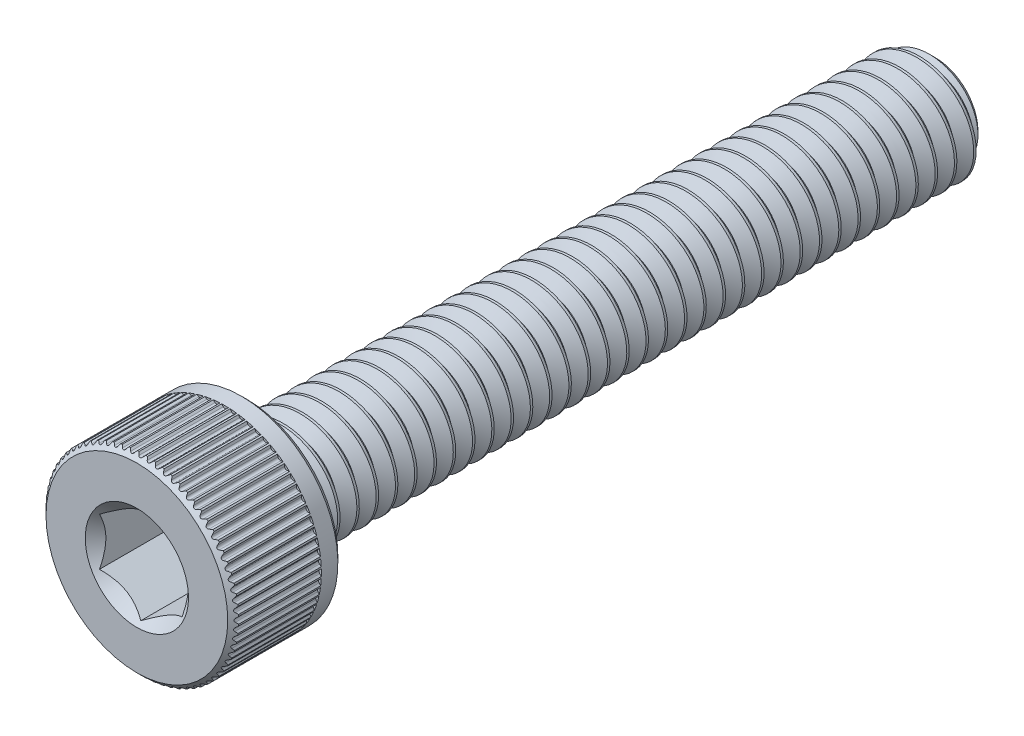
SolidWorks part; units mm, degrees
ref_plane "Front Plane" through (0, 0, 0) normal (0, 0, 1) x (1, 0, 0)
ref_plane "Top Plane" through (0, 0, 0) normal (0, 1, 0) x (1, 0, 0)
ref_plane "Right Plane" through (0, 0, 0) normal (1, 0, 0) x (0, 0, -1)
sketch "Sketch1" plane through (0, 0, 0) normal (1, 0, 0) x (0, 0, -1)
  line L0 (-14.5, 0) -> (14.5, 0) construction
  line L1 (14.5, 0) -> (14.5, 1.5453) construction
  line L2 (14.5, 1.5453) -> (14.0453, 2) construction
  line L3 (14.0453, 2) -> (13.975, 2) construction
  line L4 (13.975, 2) -> (-10.5, 2) construction
  line L5 (-10.5, 2) -> (-10.5, 3.5) construction
  line L6 (-10.5, 3.5) -> (-14.5, 3.5) construction
  line L7 (-14.5, 3.5) -> (-14.5, 0) construction
  line L8 (14.5, 1.5453) -> (14.5, 2) construction
  line L9 (14.4563, 2.0758) -> (14.8063, 1.4696) construction
  line L10 (14.8063, 1.4696) -> (15.1563, 2.0758) construction
  line L11 (15.1563, 2.0758) -> (14.4563, 2.0758) construction
  line L12 (14.8063, 2.0758) -> (14.8063, 2) construction
  line L13 (14.8063, 1.4696) -> (14.8063, 1.5453) construction
  line L14 (14.7625, 1.5453) -> (14.85, 1.5453) construction
  line L15 (14.5, 2) -> (15.1125, 2) construction
  line L16 (14.4781, 2.0379) -> (15.1344, 2.0379) construction
  line L17 (14.5, 0) -> (14.5, -2) construction
  line L18 (-10.7, 3.5) -> (-10.5, 3.3) construction
  line L19 (-14.3, 3.5) -> (-14.5, 3.3) construction
  line L20 (-10.5, 2) -> (-10.5, 0) construction
  line L21 (-10.5, 1) -> (-2.1667, 1) construction
  line L22 (-2.1667, 1) -> (6.1667, 1) construction
  line L23 (6.1667, 1) -> (14.5, 1) construction
  line L24 (-2.1667, 1) -> (-2.1667, 2) construction
  line L25 (-2.1667, 2) -> (-2.1667, 3.5) construction
  line L26 (6.1667, 1) -> (6.1667, 3.5) construction
  point P0 (-14.5, 1.5)
  point P3 (12.75, 2)
  point P4 (0, 0)
  point P18 (6.1667, 2)
  point P22 (14.8063, 1.5453)
  point P24 (13.975, 2)
  point P25 (14.8063, 2)
  point P28 (14.8063, 2.0379)
  point P29 (12.75, -2)
  point P30 (-2.1667, 2)
  point P31 (-12.5, 3.5)
  point P37 (-11.2, 3.5)
  point P38 (-14.2, 3.5)
  point P45 (-2.1667, 1)
  point P46 (6.1667, 1)
  dimension "D2" = 0.0875
  dimension "D7" = 0.2
  dimension "D8" = 0.2
  dimension "D9" = 0.2
  dimension "D10" = 0.1
  dimension "D11" = 0.5
  dimension "Drive Size" = 3
  dimension "Head Diameter" = 7
  dimension "Head Height" = 4
  dimension "Thread Pitch" = 0.7
  dimension "Thread Size" = 4
  dimension "Length" = 25
  dimension "D12" = 0.525
  dimension "D4" = 1.75
  dimension "D3" = 45
sketch "Sketch2" plane through (0, 0, 0) normal (1, 0, 0) x (0, 0, -1)
  line L0 (-14.5, 0) -> (-14.5, 3.3)
  line L1 (-14.3, 3.5) -> (-10.7, 3.5)
  line L2 (-10.5, 3.3) -> (-10.5, 2.2)
  line L4 (14.0453, 2) -> (14.5, 1.5453)
  line L5 (14.5, 1.5453) -> (14.5, 0)
  line L6 (-10.5, 3.5) -> (-14.5, 3.5) construction
  line L7 (14.5, 0) -> (-14.5, 0)
  line L8 (-14.3, 3.5) -> (-14.5, 3.3) construction
  line L10 (-14.3, 3.5) -> (-14.5, 3.3)
  line L14 (-10.7, 3.5) -> (-10.5, 3.3) construction
  line L16 (-10.7, 3.5) -> (-10.5, 3.3)
  line L17 (-10.5, 2) -> (-10.5, 3.5) construction
  line L19 (-10.3, 2) -> (14.0453, 2)
  line L20 (13.975, 2) -> (-10.5, 2) construction
  arc A1 (-10.5, 2.2) -> (-10.3, 2) centre (-10.3, 2.2) ccw
  dimension "D3" = 0.2
revolve "Revolve1" add sketch "Sketch2" angle 360 about L7
sketch "Sketch3" plane through (0, 0, 14.5) normal (0, 0, 1) x (1, 0, 0)
  line L1 (1.5, -0.866) -> (1.5, 0.866)
  line L2 (1.5, 0.866) -> (0, 1.7321)
  line L3 (0, 1.7321) -> (-1.5, 0.866)
  line L4 (-1.5, 0.866) -> (-1.5, -0.866)
  line L5 (-1.5, -0.866) -> (0, -1.7321)
  line L6 (0, -1.7321) -> (1.5, -0.866)
  circle A0 centre (0, 0) radius 1.5 construction
  circle A1 centre (0, 0) radius 3.5 construction
  circle A2 centre (0, 0) radius 3.5 construction
  circle A3 centre (0, 0) radius 1.7321 construction
  point P13 (0, 0)
extrude "Cut-Extrude1" cut sketch "Sketch3" against normal offset from surface (3 mm away) 1 up to face at (0, 3.3, 10.5)
sketch "Sketch4" plane through (0, 0, 14.5) normal (0, 0, 1) x (1, 0, 0)
  circle A0 centre (0, 0) radius 1.875
  dimension "D1" = 3.75
extrude "Cut-Extrude2" cut sketch "Sketch4" against normal up to vertex (2 mm away) draft 45 up to point (0, 3.5, 12.5)
sketch "Sketch11" plane through (0, 0, 0) normal (1, 0, 0) x (0, 0, -1)
  line L0 (-14.5, 0) -> (14.5, 0) construction
  line L1 (-14.5, 0) -> (14.5, 0) construction
  line L2 (-5.8125, 0) -> (-5.8125, 2) construction
  line L3 (13.975, 2) -> (-10.5, 2) construction
  line L4 (9.8125, 0) -> (9.8125, 2) construction
  line L6 (14.5, 1.5453) -> (14.5, 2) construction
  point P2 (-5.8125, 0)
  point P3 (9.8125, 0)
  dimension "D1" = 4.6875
  dimension "D2" = 4.6875
sketch "Sketch6" plane through (0, 0, -14.5) normal (0, 0, -1) x (-1, 0, 0)
  circle A0 centre (0, 0) radius 2
curve "Helix/Spiral1" pitch 0.7 height 25.7 turns 36.7143
sketch "Sketch10" plane through (0, 0, 0) normal (1, 0, 0) x (0, 0, -1)
  line L0 (-10.3, -3.5) -> (-10.3, 3.5)
  line L5 (-14.5, 0) -> (14.5, 0) construction
  line L6 (-10.3, 2) -> (-10.3, -2) construction
  point P3 (-10.3, 0)
split "Split1" trim tools "Sketch10" bodies to split 106 resulting bodies 114 115
sketch "Sketch7" plane through (0, 0, 0) normal (1, 0, 0) x (0, 0, -1)
  line L0 (14.4781, 2.0379) -> (15.1344, 2.0379)
  line L1 (15.1344, 2.0379) -> (14.85, 1.5453)
  line L2 (14.85, 1.5453) -> (14.7625, 1.5453)
  line L3 (14.7625, 1.5453) -> (14.4781, 2.0379)
sweep "Cut-Sweep1" cut profiles "Sketch7" path "Helix/Spiral1"
sketch "Sketch8" plane through (0, 0, 0) normal (1, 0, 0) x (0, 0, -1)
  line L0 (-10.5, 0) -> (-10.5, 2)
  line L1 (-10.3, -2) -> (-10.3, 2) construction
  line L2 (-10.5, 2) -> (-10.3, 2)
  line L4 (-10.3, 2) -> (-9.1453, 0)
  line L5 (-9.1453, 0) -> (-10.5, 0)
  line L6 (13.975, 2) -> (-10.5, 2) construction
  line L7 (-14.5, 0) -> (14.5, 0) construction
  dimension "D1" = 60
revolve "Revolve2" add sketch "Sketch8" angle 360 about L5
ref_plane "Plane1" through (0, 0, 14.5) normal (0, 0, 1) x (1, 0, 0)
sketch "Sketch12" plane through (0, 0, 14.5) normal (0, 0, 1) x (1, 0, 0)
  line L0 (0, 0) -> (0.1221, 3.4979) construction
  line L1 (0, 0) -> (-0.1221, 3.4979) construction
  line L2 (0, 3.4125) -> (0, 3.5875) construction
  line L3 (-0.2118, 3.5875) -> (0.2118, 3.5875)
  line L4 (-0.2118, 3.5875) -> (-0.0628, 3.4385)
  line L5 (0.0628, 3.4385) -> (0.2118, 3.5875)
  circle A0 centre (0, 0) radius 3.5 construction
  arc A1 (-0.0628, 3.4385) -> (0.0628, 3.4385) centre (0, 3.5013) ccw
  point P9 (0, 3.5875)
  point P13 (0, 3.5)
  dimension "D1" = 4
  dimension "D2" = 0.0875
extrude "Cut-Extrude3" cut sketch "Sketch12" against normal blind 3.2
pattern_circular "CirPattern1" count 72 over 360 about axis through (0, 0, 0) along (0, 0, 1) of "Cut-Extrude3"
equation "\"D2@Sketch1\" = \"Thread Pitch@Sketch1\" / 8"
equation "\"D4@Helix/Spiral1\" = \"Thread Pitch@Sketch1\""
equation "\"D7@Sketch1\" = \"Head Height@Sketch1\" * .05"
equation "\"D8@Sketch1\"=\"D7@Sketch1\""
equation "\"D9@Sketch1\"=\"D7@Sketch1\""
equation "\"D10@Sketch1\"=\"D7@Sketch1\"/2"
equation "\"D11@Sketch1\"=\"D10@Sketch1\"*5"
equation "\"D4@Sketch1\"=\"Thread Pitch@Sketch1\"*2.5"
equation "\"D12@Sketch1\"=\"Thread Pitch@Sketch1\"*.75"
equation "\"D3@Helix/Spiral1\"=\"Length@Sketch1\"+\"Thread Pitch@Sketch1\""
equation "\"D3@Sketch2\" = \"Thread Size@Sketch1\" * 0.05"
equation "\"D1@Sketch11\"=\"Length@Sketch1\"*0.1875"
equation "\"D2@Sketch11\"=\"D1@Sketch11\""
equation "\"D2@Sketch12\"=\"Head Diameter@Sketch1\"*.0125"
equation "\"D1@Cut-Extrude3\"=\"Head Height@Sketch1\"*.8"
equation "\"D1@CirPattern1\"=\"D3@CirPattern1\"/(1.25*\"D1@Sketch12\")"
equation "\"D1@Sketch4\"=\"Drive Size@Sketch1\"*1.25"
